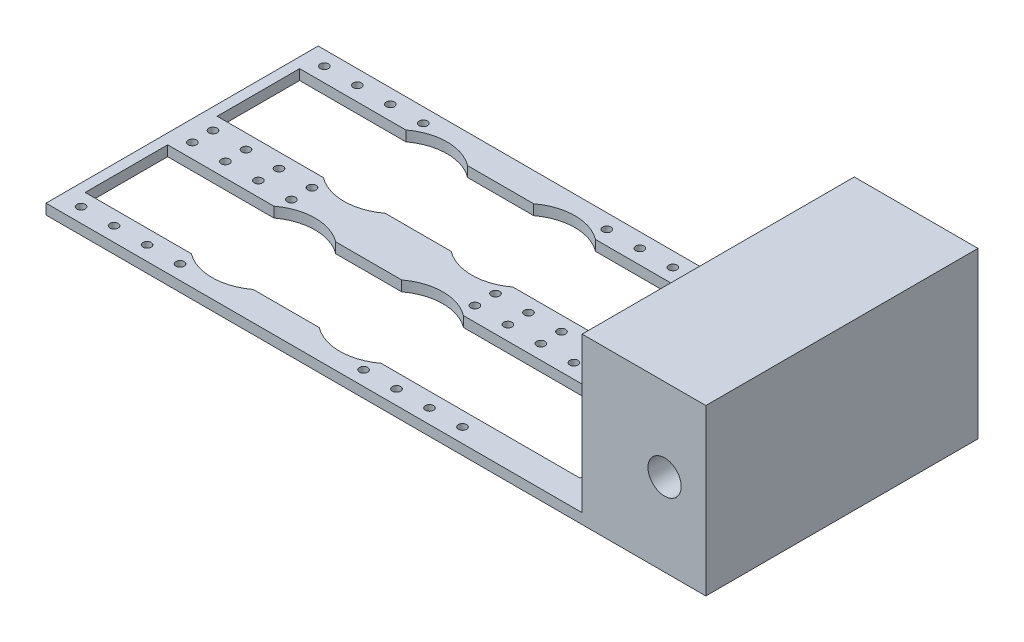
SolidWorks part; units mm, degrees
ref_plane "Front Plane" through (0, 0, 0) normal (0, 0, 1) x (1, 0, 0)
ref_plane "Top Plane" through (0, 0, 0) normal (0, 1, 0) x (1, 0, 0)
ref_plane "Right Plane" through (0, 0, 0) normal (1, 0, 0) x (0, 0, -1)
sketch "Sketch1" plane through (0, 0, 0) normal (0, 1, 0) x (1, 0, 0)
  line L1 (-80, 33) -> (80, 33)
  line L2 (-80, 33) -> (-80, -33)
  line L3 (-80, -33) -> (80, -33)
  line L4 (80, 33) -> (80, -33)
  line L5 (-80, 33) -> (80, -33) construction
  line L6 (-80, -33) -> (80, 33) construction
  point P0 (0, 0)
  dimension "D1" = 160
  dimension "D2" = 66
extrude "Boss-Extrude1" add sketch "Sketch1" along normal blind 40
sketch "Sketch2" plane through (0, 0, 33) normal (0, 0, 1) x (1, 0, 0)
  line L0 (80, 40) -> (80, 0) construction
  line L1 (-80, 40) -> (80, 40) construction
  line L2 (-80, 40) -> (50, 40)
  line L3 (-80, 40) -> (-80, 2.5)
  line L4 (-80, 2.5) -> (50, 2.5)
  line L5 (50, 40) -> (50, 2.5)
  line L6 (-80, 40) -> (50, 2.5) construction
  line L7 (-80, 2.5) -> (50, 40) construction
  line L8 (-80, 40) -> (-80, 0) construction
  circle A0 centre (70, 20) radius 4.025
  point P4 (80, 20)
  point P5 (-15, 21.25)
  dimension "D1" = 8.05
  dimension "D2" = 10
  dimension "D3" = 37.5
  dimension "D4" = 130
extrude "Cut-Extrude1" cut sketch "Sketch2" against normal through all
sketch "Sketch3" plane through (0, 40, 0) normal (0, 1, 0) x (1, 0, 0)
  line L0 (-80, 33) -> (-80, -33) construction
  line L1 (80, 33) -> (50, 33) construction
  line L2 (-75, 29.5) -> (-67, 29.5) construction
  line L3 (-75, 2.5) -> (-67, 2.5) construction
  line L4 (0, 0) -> (13.7346, 0) construction
  line L5 (-80, 33) -> (-80, -33) construction
  line L6 (-6.5, 29.5) -> (1.5, 29.5) construction
  line L7 (-75, 29.5) -> (-75, 2.5) construction
  line L8 (-77.5, 26) -> (42.5, 26)
  line L9 (-77.5, 26) -> (-77.5, 6)
  line L10 (-77.5, 6) -> (42.5, 6)
  line L11 (42.5, 26) -> (42.5, 6)
  line L12 (-6.5, 2.5) -> (1.5, 2.5) construction
  line L13 (-6.5, -2.5) -> (1.5, -2.5) construction
  line L14 (-75, -29.5) -> (-75, -2.5) construction
  line L15 (-6.5, -29.5) -> (1.5, -29.5) construction
  line L16 (-75, -2.5) -> (-67, -2.5) construction
  line L17 (-75, -29.5) -> (-67, -29.5) construction
  line L18 (42.5, -26) -> (42.5, -6)
  line L19 (-77.5, -6) -> (42.5, -6)
  line L20 (-77.5, -26) -> (-77.5, -6)
  line L21 (-77.5, -26) -> (42.5, -26)
  circle A0 centre (-75, 29.5) radius 1
  circle A1 centre (-75, 2.5) radius 1
  circle A2 centre (-67, 29.5) radius 1
  circle A3 centre (-59, 29.5) radius 1
  circle A4 centre (-51, 29.5) radius 1
  circle A11 centre (-67, 2.5) radius 1
  circle A12 centre (-59, 2.5) radius 1
  circle A13 centre (-51, 2.5) radius 1
  circle A50 centre (-6.5, 29.5) radius 1
  circle A51 centre (-6.5, 2.5) radius 1
  circle A52 centre (1.5, 29.5) radius 1
  circle A53 centre (9.5, 29.5) radius 1
  circle A54 centre (17.5, 29.5) radius 1
  circle A55 centre (1.5, 2.5) radius 1
  circle A56 centre (9.5, 2.5) radius 1
  circle A57 centre (17.5, 2.5) radius 1
  circle A58 centre (17.5, -2.5) radius 1
  circle A59 centre (9.5, -2.5) radius 1
  circle A60 centre (1.5, -2.5) radius 1
  circle A61 centre (17.5, -29.5) radius 1
  circle A62 centre (9.5, -29.5) radius 1
  circle A63 centre (1.5, -29.5) radius 1
  circle A64 centre (-6.5, -2.5) radius 1
  circle A65 centre (-6.5, -29.5) radius 1
  circle A66 centre (-51, -2.5) radius 1
  circle A67 centre (-59, -2.5) radius 1
  circle A68 centre (-67, -2.5) radius 1
  circle A69 centre (-51, -29.5) radius 1
  circle A70 centre (-59, -29.5) radius 1
  circle A71 centre (-67, -29.5) radius 1
  circle A72 centre (-75, -2.5) radius 1
  circle A73 centre (-75, -29.5) radius 1
  point P96 (-77.5, 16)
  point P97 (-75, 16)
  dimension "D1" = 2
  dimension "D3" = 3.5
  dimension "D4" = 27
  dimension "D12" = 2
  dimension "D2" = 5
  dimension "D6" = 8
  dimension "D8" = 8
  dimension "D9" = 20
  dimension "D10" = 120
  dimension "D11" = 2.5
  dimension "D13" = 44.5
  dimension "D15" = 8
  dimension "D17" = 8
  dimension "D5" = 4
  dimension "D7" = 4
  dimension "D14" = 4
  dimension "D16" = 4
extrude "Cut-Extrude2" cut sketch "Sketch3" against normal through all
sketch "Sketch4" plane through (0, 2.5, 0) normal (0, 1, 0) x (1, 0, 0)
  line L1 (-77.5, -6) -> (42.5, -6) construction
  line L2 (-77.5, 26) -> (42.5, 26) construction
  circle A0 centre (-44.25, -16) radius 12.5
  circle A1 centre (-51, -2.5) radius 1 construction
  circle A2 centre (-44.25, 16) radius 12.5
  circle A3 centre (-13.25, 16) radius 12.5
  circle A4 centre (-13.25, -16) radius 12.5
  circle A5 centre (-6.5, -2.5) radius 1 construction
  dimension "D1" = 25
  dimension "D4" = 6.75
  dimension "D2" = 6.75
  dimension "D3" = 10
  dimension "D5" = 10
extrude "Cut-Extrude3" cut sketch "Sketch4" against normal through all
sketch "Sketch5" plane through (0, 40, 0) normal (0, 1, 0) x (1, 0, 0)
  line L0 (80, 33) -> (50, 33) construction
  line L1 (45, 33) -> (80, 33)
  line L2 (45, 33) -> (45, -33)
  line L3 (45, -33) -> (80, -33)
  line L4 (80, 33) -> (80, -33)
  line L5 (45, 33) -> (80, -33) construction
  line L6 (45, -33) -> (80, 33) construction
  line L7 (42.5, -6) -> (42.5, -26) construction
  point P0 (62.5, 0)
  dimension "D1" = 2.5
